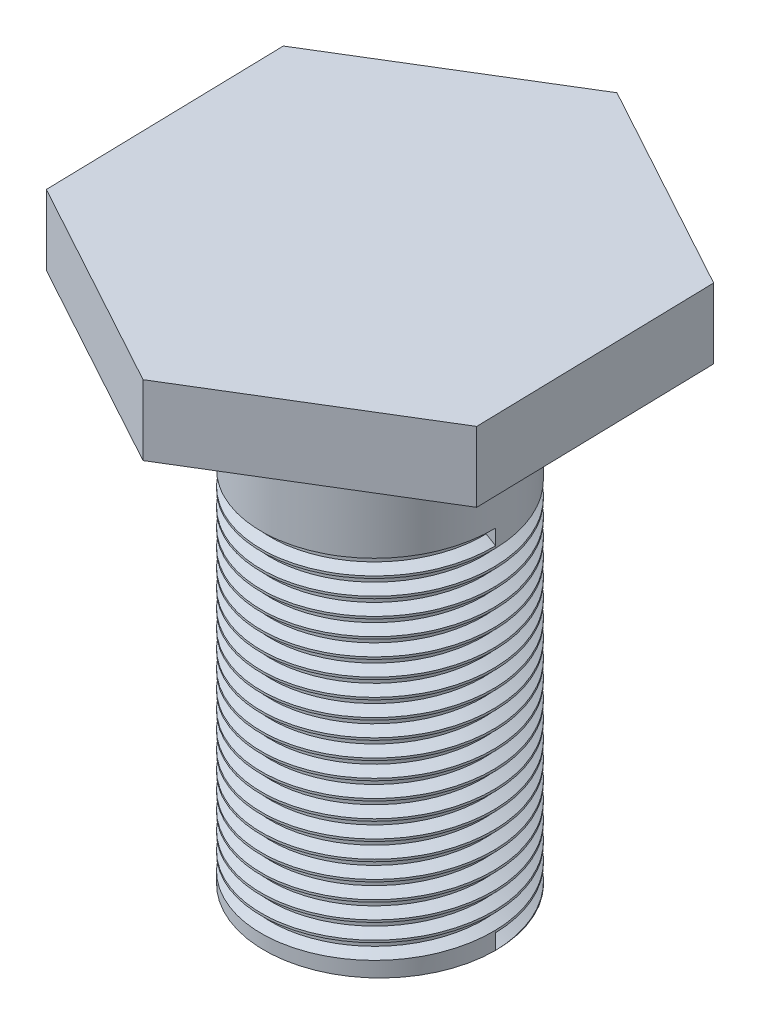
SolidWorks part; units mm, degrees
material "Alloy Steel"
ref_plane "Front Plane" through (0, 0, 0) normal (0, 0, 1) x (1, 0, 0)
ref_plane "Top Plane" through (0, 0, 0) normal (0, 1, 0) x (1, 0, 0)
ref_plane "Right Plane" through (0, 0, 0) normal (1, 0, 0) x (0, 0, -1)
sketch "Sketch1" plane through (0, 0, 0) normal (0, 1, 0) x (1, 0, 0)
  circle A0 centre (0, 0) radius 1.65
  dimension "D1" = 3.3
extrude "Boss-Extrude1" add sketch "Sketch1" along normal blind 7
sketch "Sketch2" plane through (0, 7, 0) normal (0, 1, 0) x (1, 0, 0)
  line L1 (3.0403, -1.6604) -> (2.958, 1.8028)
  line L2 (2.958, 1.8028) -> (-0.0822, 3.4631)
  line L3 (-0.0822, 3.4631) -> (-3.0403, 1.6604)
  line L4 (-3.0403, 1.6604) -> (-2.958, -1.8028)
  line L5 (-2.958, -1.8028) -> (0.0822, -3.4631)
  line L6 (0.0822, -3.4631) -> (3.0403, -1.6604)
  circle A1 centre (0, 0) radius 3 construction
  dimension "D1" = 6
extrude "Boss-Extrude2" add sketch "Sketch2" along normal blind 1
thread "Thread1" pitch 0.25 method cut profile "Thread Profile1" start angle 0, offset 0, length 5, pitch 0.25, diameter 3.3
ref_plane "Plane1" through (1.65, 0, 0) normal (0, 0, 1) x (1, 0, 0)
sketch "Thread Profile1" plane through (1.65, 0, 0) normal (0, 0, 1) x (1, 0, 0)
  line L0 (0, 0) -> (0, 0.25) construction
  line L11 (0, 0) -> (0, 0.2187)
  line L12 (0, 0.2187) -> (-0.1353, 0.1406)
  line L13 (-0.1353, 0.1406) -> (-0.1353, 0.0781)
  line L15 (-0.1353, 0.0781) -> (0, 0)
  line L17 (-0.1353, 0.1094) -> (0, 0.1094) construction
  point P2 (0, 0)
  dimension "Pitch" = 0.25
  dimension "Profile_Angle" = 60
  dimension "Profile_Land" = 0.0625
  dimension "Profile_Height" = 0.1353
